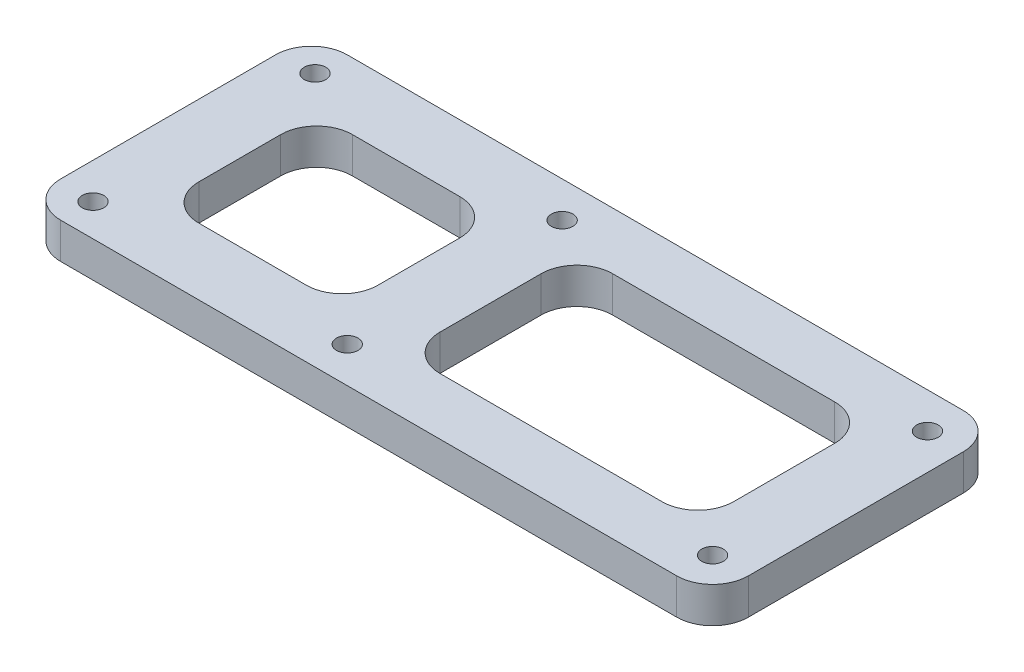
SolidWorks part; units mm, degrees
material "Acrylic (Medium-high impact)"
ref_plane "Front Plane" through (0, 0, 0) normal (0, 0, 1) x (1, 0, 0)
ref_plane "Top Plane" through (0, 0, 0) normal (0, 1, 0) x (1, 0, 0)
ref_plane "Right Plane" through (0, 0, 0) normal (1, 0, 0) x (0, 0, -1)
sketch "Sketch1" plane through (0, 0, 0) normal (0, 1, 0) x (1, 0, 0)
  line L0 (0, 15) -> (0, -15)
  line L5 (0, 0) -> (15.4905, 0)
  line L6 (-40, 20) -> (56, 20)
  line L7 (0, 15) -> (-35, 15)
  line L8 (-35, 15) -> (-35, 15.5)
  line L9 (-40, 20) -> (-40, -20)
  line L10 (0, -15) -> (51, -15)
  line L11 (-40, -20) -> (56, -20)
  line L12 (56, 20) -> (56, -20)
  line L13 (-35, 15) -> (0, -15)
  line L14 (0, 15) -> (-35, -15.5)
  line L15 (0, 15) -> (51, -15)
  line L16 (51, 15) -> (0, -15)
  line L18 (-5, -10.7143) -> (-30, -10.7143)
  line L19 (-5, -10.7143) -> (-5, 10.7143)
  line L20 (-5, 10.7143) -> (-30, 10.7143)
  line L21 (-30, -10.7143) -> (-30, 10.7143)
  line L22 (-5, -10.7143) -> (-30, 10.7143) construction
  line L23 (-5, 10.7143) -> (-30, -10.7143) construction
  line L24 (46, -12.0588) -> (5, -12.0588)
  line L25 (46, -12.0588) -> (46, 12.0588)
  line L26 (46, 12.0588) -> (5, 12.0588)
  line L27 (5, -12.0588) -> (5, 12.0588)
  line L28 (46, -12.0588) -> (5, 12.0588) construction
  line L29 (46, 12.0588) -> (5, -12.0588) construction
  circle A0 centre (-35, 15.5) radius 1.5
  circle A1 centre (0, 15) radius 1.5
  circle A2 centre (51, -15) radius 1.5
  circle A3 centre (-35, -15.5) radius 1.5
  circle A4 centre (0, -15) radius 1.5
  circle A5 centre (51, 15) radius 1.5
  point P0 (0, 0)
  point P21 (-17.5, 0)
  point P26 (25.5, 0)
  dimension "D10" = 3
  dimension "D11" = 3
  dimension "D12" = 3
  dimension "D1" = 15
  dimension "D2" = 15
  dimension "D3" = 56
  dimension "D4" = 0.5
  dimension "D5" = 35
  dimension "D6" = 40
  dimension "D7" = 51
  dimension "D8" = 40
  dimension "D9" = 5
  dimension "D13" = 5
  dimension "D14" = 5
extrude "Boss-Extrude1" add sketch "Sketch1" along normal blind 5 contours L12 L6 L9 L11 A5 L25 L15 A2 L10 A4 L13 L18 A3 L21 A0 L7 A1 L26 | L13 A4 L0 A1 L14 L19 | A1 L7 A0 L13 L20 L19 L14 | A1 L0 L5 L27 L15 | L0 A4 L16 L27 L5 | L16 A4 L10 A2 L15 L24 region at (2.4434, 0, -6.6616) region at (-2.3896, 0, 0.0161) region at (-17.5113, 0, -12.9565) region at (2.4434, 0, 6.6616) region at (25.5, 0, 13.5724) region at (8, 0, -18.96)
fillet "Fillet1" radius 5 12 edges at (46, 2.5, 12.0588) (5, 2.5, 12.0588) (46, 2.5, -12.0588) (5, 2.5, -12.0588) (-5, 2.5, 10.7143) (-30, 2.5, 10.7143) (-5, 2.5, -10.7143) (-30, 2.5, -10.7143) (56, 2.5, -20) (56, 2.5, 20) (-40, 2.5, 20) (-40, 2.5, -20)
